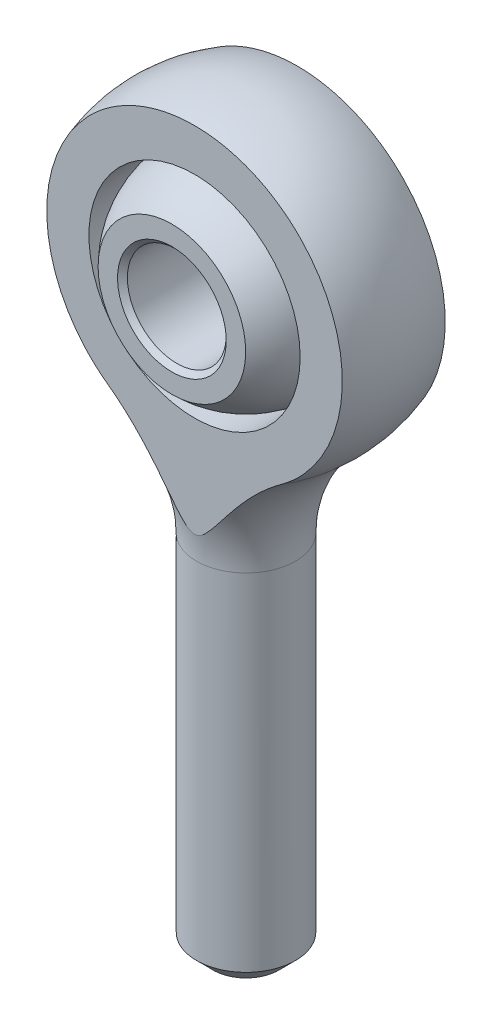
SolidWorks part; units mm, degrees
material "1023 Carbon Steel Sheet (SS)"
ref_plane "Front" through (0, 0, 0) normal (0, 0, 1) x (1, 0, 0)
ref_plane "Top" through (0, 0, 0) normal (0, 1, 0) x (1, 0, 0)
ref_plane "Right" through (0, 0, 0) normal (1, 0, 0) x (0, 0, -1)
sketch "Sketch1" plane through (0, 0, 0) normal (0, 0, 1) x (1, 0, 0)
  line L0 (0, 0) -> (0, -22)
  line L1 (0, -22) -> (3, -22)
  line L2 (3, -22) -> (3, 0)
  line L3 (3, 0) -> (0, 0)
  line L5 (0, 23.5) -> (0, 0) construction
  line L6 (0, 23.5) -> (9.5, 23.5) construction
  line L7 (9.5, 23.5) -> (9.5, 14) construction
  line L8 (-3, -22) -> (-3, 0) construction
  arc A0 (6.1306, 6.7429) -> (0, 23.5) centre (0, 14) ccw construction
  circle A1 centre (0, 14) radius 3 construction
  circle A2 centre (0, 14) radius 6.35 construction
  circle A3 centre (0, 14) radius 6.4135 construction
  arc A4 (3, 0) -> (6.1306, 6.7429) centre (11.8269, 0) cw construction
  point P16 (-3, -16.25)
  dimension "A" = 6
  dimension "Ball Dia" = 12.7
  dimension "B" = 19
  dimension "D1" = 12.827
  dimension "D" = 36
  dimension "E" = 22
  dimension "Thread Dia" = 6
  dimension "D2" = 5.75
revolve "Revolve1" add sketch "Sketch1" angle 360 about L5
sketch "Sketch12" plane through (0, -22, 0) normal (0, -1, 0) x (1, 0, 0)
  circle A1 centre (0, 0) radius 3
  circle A2 centre (0, 0) radius 3
  dimension "D1" = 0
curve "Helix/Spiral1" [suppressed] pitch 1 height 23 turns 23 parameters "pitch"=1
chamfer "Chamfer2" distance 1 angle 45 1 edges at (-3, -22, 0)
sketch "Sketch13" plane through (0, 0, 0) normal (1, 0, 0) x (0, 0, -1)
  line L0 (-3, -22.875) -> (-3, -22)
  line L1 (-3, -22) -> (-2.3505, -22.375)
  line L2 (-2.3505, -22.375) -> (-2.3505, -22.5)
  line L3 (-2.3505, -22.5) -> (-3, -22.875)
  line L4 (-2.3505, -22.4375) -> (-3, -22.4375) construction
  line L5 (-2.6752, -22.6875) -> (-2.6752, -22.1875) construction
  line L6 (-3, -22) -> (3, -22) construction
  dimension "D1" = 60
  dimension "D3" = 0.5
sweep "Cut-Sweep1" [suppressed] cut profiles "Sketch13" path "Helix/Spiral1"
sketch "Sketch4" plane through (0, 0, 0) normal (0, 0, 1) x (1, 0, 0)
  line L0 (3, 0) -> (0, 0) construction
  line L2 (0, 23.5) -> (0, 0) construction
  line L3 (3, 0) -> (0, 0)
  line L5 (0, 23.5) -> (0, 0)
  line L6 (0, 23.5) -> (0, 26.04) construction
  arc A0 (6.1306, 6.7429) -> (0, 23.5) centre (0, 14) ccw construction
  arc A1 (6.1306, 6.7429) -> (0, 23.5) centre (0, 14) ccw
  arc A2 (6.1306, 6.7429) -> (3, 0) centre (11.8269, 0) ccw construction
  arc A3 (6.1306, 6.7429) -> (3, 0) centre (11.8269, 0) ccw
  dimension "D1" = 2.54
revolve "Revolve2" add sketch "Sketch4" angle 360 about L6
sketch "Sketch5" plane through (0, 0, 0) normal (1, 0, 0) x (0, 0, -1)
  line L0 (3.125, 23.5) -> (9.5, 23.5)
  line L1 (-3.125, 23.5) -> (3.125, 23.5) construction
  line L2 (-3.125, 23.5) -> (-3.125, 1.25)
  line L3 (-3, 0) -> (3, 0) construction
  line L4 (3.125, 23.5) -> (3.125, 1.25)
  line L5 (9.5, 23.5) -> (9.5, 0)
  line L6 (9.5, 0) -> (3, 0)
  line L7 (-3, 0) -> (-9.5, 0)
  line L8 (-9.5, 0) -> (-9.5, 23.5)
  line L9 (-9.5, 23.5) -> (-3.125, 23.5)
  line L10 (3, 0) -> (3.125, 1.25)
  line L11 (-3, 0) -> (-3.125, 1.25)
  line L12 (-3.125, 1.25) -> (3.125, 1.25) construction
  line L13 (0, 0) -> (0, 1.25) construction
  arc A0 (6.1306, 6.7429) -> (-6.1306, 6.7429) centre (0, 14) ccw construction
  dimension "F" = 6.25
  dimension "D2" = 1.25
extrude "Cut-Extrude1" cut sketch "Sketch5" against normal through all and the other way through all
sketch "Sketch6" plane through (0, 0, 0) normal (0, 0, 1) x (1, 0, 0)
  circle A0 centre (0, 14) radius 6.4135 construction
  circle A1 centre (0, 14) radius 6.4135
extrude "Cut-Extrude2" cut sketch "Sketch6" against normal through all and the other way through all
sketch "Sketch7" plane through (0, 0, 0) normal (0, 0, 1) x (1, 0, 0)
  line L0 (0, 20.35) -> (0, 7.65)
  line L1 (0, 23.5) -> (0, 0) construction
  line L2 (0, 0) -> (0, 7.65) construction
  arc A0 (0, 7.65) -> (0, 20.35) centre (0, 14) ccw
  circle A1 centre (0, 14) radius 6.35 construction
revolve "Revolve3" add sketch "Sketch7" angle 360 about L2
sketch "Sketch8" plane through (0, 0, 0) normal (1, 0, 0) x (0, 0, -1)
  line L0 (-3.125, 23.5) -> (3.125, 23.5) construction
  line L1 (-4.5, 23.5) -> (4.5, 23.5) construction
  line L2 (-4.5, 23.5) -> (-4.5, 0)
  line L3 (-4.5, 0) -> (4.5, 0) construction
  line L4 (4.5, 23.5) -> (4.5, 0)
  line L5 (4.5, 23.5) -> (9.5, 23.5)
  line L6 (9.5, 23.5) -> (9.5, 0)
  line L7 (9.5, 0) -> (4.5, 0)
  line L8 (-4.5, 0) -> (-9.5, 0)
  line L9 (-9.5, 0) -> (-9.5, 23.5)
  line L10 (-9.5, 23.5) -> (-4.5, 23.5)
  dimension "C" = 9
extrude "Cut-Extrude3" cut sketch "Sketch8" against normal through all and the other way through all
sketch "Sketch10" plane through (0, 0, 0) normal (0, 0, 1) x (1, 0, 0)
  circle A0 centre (0, 14) radius 3 construction
  circle A1 centre (0, 14) radius 3
extrude "Cut-Extrude4" cut sketch "Sketch10" against normal through all and the other way through all
chamfer "Chamfer1" distance 0.3 angle 45 2 edges at (3, 14, -4.5) (3, 14, 4.5)
sketch "Sketch11" plane through (0, 0, 0) normal (1, 0, 0) x (0, 0, -1)
  line L0 (0, 14) -> (-4.5, 14.9155) construction
  line L1 (3.125, 14) -> (-3.125, 14) construction
  line L2 (0, 14) -> (-4.5, 13.0845) construction
  line L3 (0, 23.5) -> (0, 0) construction
  line L4 (-4.5, 23.5) -> (-4.5, 0) construction
  line L5 (0, 14) -> (0.0074, 14) construction
  dimension "Swivel" = 23
equation "\"D1@Sketch1\"=\"Ball Dia@Sketch1\"*1.01"
equation "\"D1@Chamfer1\"=\"A@Sketch1\"/20"
equation "\"D1@Sketch5\"=\"Thread Dia@Sketch1\""
equation "\"D2@Sketch5\"=\"F@Sketch5\"/5"
equation "\"D2@Sketch13\" = \"pitch@Helix/Spiral1\"*.125"
equation "\"D3@Sketch13\" = \"pitch@Helix/Spiral1\"*.50"
equation "\"D3@Helix/Spiral1\" = \"E@Sketch1\"+\"pitch@Helix/Spiral1\""
equation "\"D1@Chamfer2\" = \"pitch@Helix/Spiral1\""
equation "\"D2@Sketch1\" = \"pitch@Helix/Spiral1\"*5.75"
